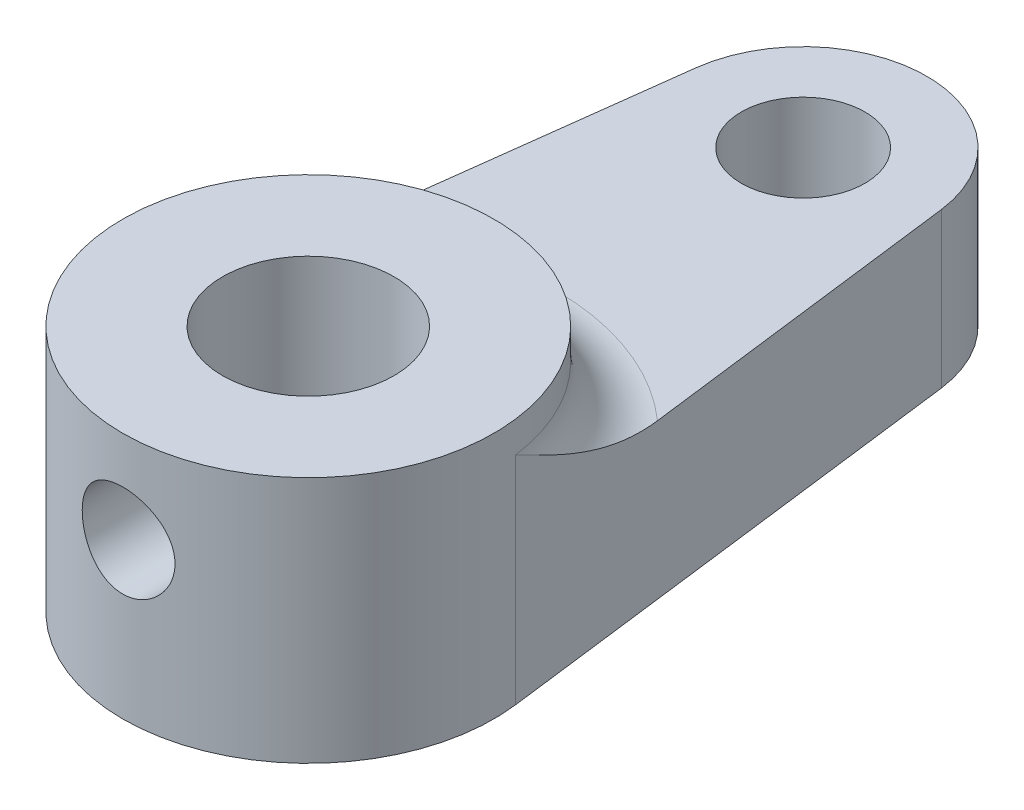
SolidWorks part; units mm, degrees
ref_plane "Front Plane" through (0, 0, 0) normal (0, 0, 1) x (1, 0, 0)
ref_plane "Top Plane" through (0, 0, 0) normal (0, 1, 0) x (1, 0, 0)
ref_plane "Right Plane" through (0, 0, 0) normal (1, 0, 0) x (0, 0, -1)
sketch "Sketch1" plane through (0, 0, 0) normal (0, 1, 0) x (1, 0, 0)
  line L0 (-5.9529, 0.75) -> (-3.9686, 16.5)
  line L1 (5.9529, 0.75) -> (3.9686, 16.5)
  circle A0 centre (0, 0) radius 2.7736
  arc A1 (-5.9529, 0.75) -> (5.9529, 0.75) centre (0, 0) ccw
  arc A2 (3.9686, 16.5) -> (-3.9686, 16.5) centre (0, 16) ccw
  circle A3 centre (0, 16) radius 2
  dimension "D1" = 8
  dimension "D3" = 4
  dimension "D4" = 6
  dimension "D2" = 16
extrude "Boss-Extrude1" add sketch "Sketch1" along normal mid plane 5
sketch "Sketch2" plane through (0, 2.5, 0) normal (0, 1, 0) x (1, 0, 0)
  circle A0 centre (0, 0) radius 6
  circle A1 centre (0, 0) radius 2.7736 construction
  circle A2 centre (0, 0) radius 2.7736
extrude "Boss-Extrude2" add sketch "Sketch2" along normal blind 3
fillet "Fillet1" radius 2 1 edges at (0, 2.5, -6)
sketch "Sketch3" plane through (0, 0, 0) normal (0, 0, 1) x (1, 0, 0)
  line L0 (-6, -2.5) -> (6, -2.5) construction
  circle A0 centre (0, 2.5) radius 1.5
  dimension "D1" = 3
  dimension "D2" = 5
extrude "Cut-Extrude1" cut sketch "Sketch3" along normal blind 19
